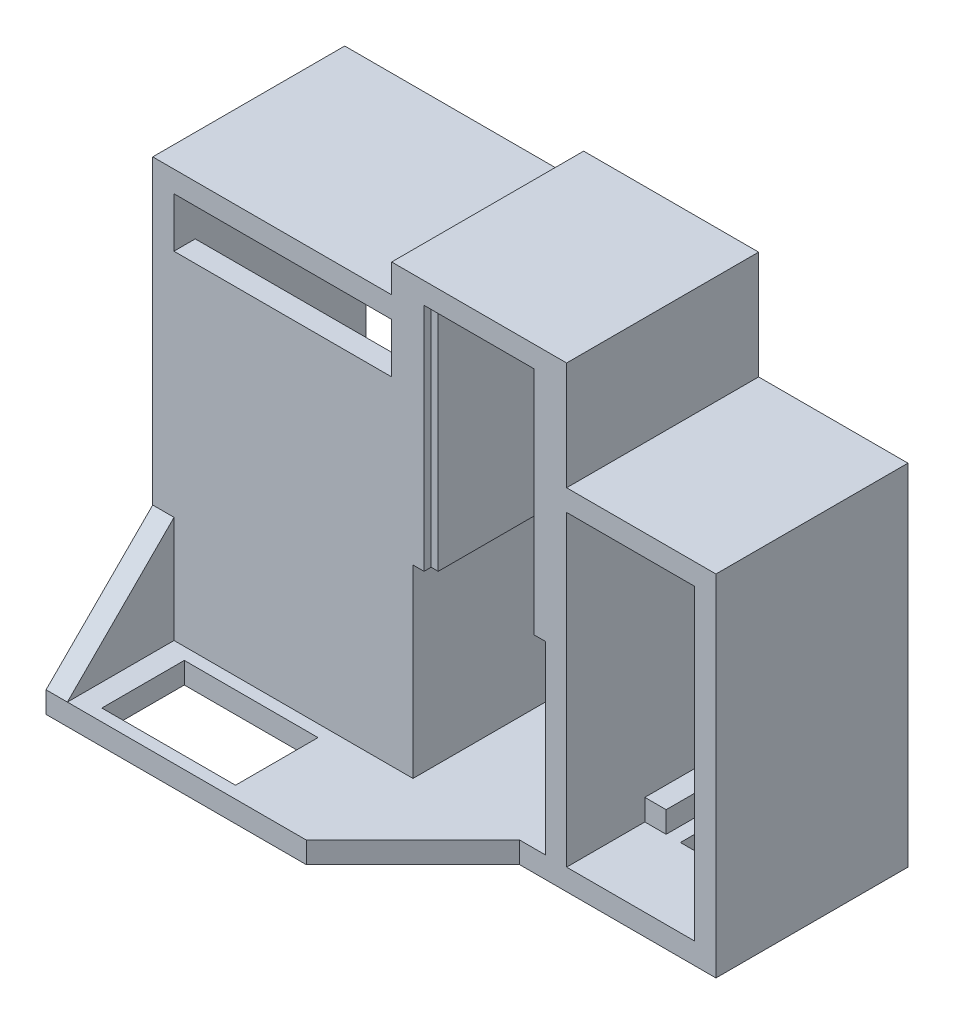
SolidWorks part; units mm, degrees
ref_plane "Front Plane" through (0, 0, 0) normal (0, 0, 1) x (1, 0, 0)
ref_plane "Top Plane" through (0, 0, 0) normal (0, 1, 0) x (1, 0, 0)
ref_plane "Right Plane" through (0, 0, 0) normal (1, 0, 0) x (0, 0, -1)
sketch "Sketch1" plane through (0, 0, 0) normal (0, 0, 1) x (1, 0, 0)
  line L0 (0, 0) -> (-18.6, 0)
  line L1 (-18.6, 0) -> (-18.6, 26)
  line L2 (-18.6, 26) -> (0, 26)
  line L3 (0, 26) -> (0, 0)
  line L4 (-18.6, 26) -> (-17.05, 26)
  line L5 (-17.05, 26) -> (-17.05, 58.4)
  line L6 (-17.05, 58.4) -> (-1.55, 58.4)
  line L7 (-1.55, 58.4) -> (-1.55, 26)
  line L8 (-18.6, 0) -> (-21.6, 0)
  line L9 (-21.6, 0) -> (-21.6, 58.4)
  line L10 (-21.6, 58.4) -> (-21.6, 61.4)
  line L11 (-21.6, 61.4) -> (-18.6, 61.4)
  line L12 (-18.6, 61.4) -> (-18.6, 26)
  line L13 (-18.6, 61.4) -> (0, 61.4)
  line L14 (0, 61.4) -> (0, 26)
  line L15 (0, 61.4) -> (3, 61.4)
  line L16 (3, 61.4) -> (3, 0)
  line L17 (3, 0) -> (0, 0)
  line L18 (3, 0) -> (3, -3)
  line L19 (3, -3) -> (-21.6, -3)
  line L20 (-21.6, -3) -> (-21.6, 0)
  line L21 (-21.6, 58.4) -> (3, 58.4)
  line L22 (-17.05, 58.4) -> (-16.05, 58.4)
  line L23 (-16.05, 58.4) -> (-16.05, 26)
  line L24 (-16.05, 26) -> (-17.05, 26)
  line L25 (-1.55, 58.4) -> (-2.55, 58.4)
  line L26 (-2.55, 58.4) -> (-2.55, 26)
  line L27 (-2.55, 26) -> (-1.55, 26)
extrude "Boss-Extrude1" add sketch "Sketch1" along normal blind 3 contours L23 L6 L5 L2 | L26 L21 L23 L2 | L6 L26 L2 L7 | L21 L7 L2 L14 | L21 L12 L2 L5 | L21 L9 L8 L1 L12 | L10 L21 L12 L11 | L12 L21 L6 L14 L13 | L14 L21 L16 L15 | L21 L14 L3 L17 L16 | L3 L2 L1 L0 | L20 L19 L18 L17 L0 L8 region at (-9.3, -1.5, 0) region at (-9.3, 13, 0) region at (1.5, 29.2, 0) region at (-20.1, 29.2, 0) region at (-0.775, 42.2, 0) region at (-17.825, 42.2, 0) region at (-2.05, 42.2, 0) region at (-9.3, 59.9, 0) region at (1.5, 59.9, 0) region at (-16.55, 42.2, 0) region at (-20.1, 59.9, 0) region at (-9.3, 42.2, 0)
extrude "Boss-Extrude2" add sketch "Sketch1<5>" along normal blind 26 contours L10 L21 L12 L11 | L12 L21 L6 L14 L13 | L6 L26 L2 L7 | L21 L7 L2 L14 | L23 L6 L5 L2 | L21 L12 L2 L5 | L21 L9 L8 L1 L12 | L14 L21 L16 L15 | L21 L14 L3 L17 L16 | L20 L19 L18 L17 L0 L8 region at (-9.3, -1.5, 0) region at (1.5, 29.2, 0) region at (-20.1, 29.2, 0) region at (-0.775, 42.2, 0) region at (-17.825, 42.2, 0) region at (-2.05, 42.2, 0) region at (-9.3, 59.9, 0) region at (1.5, 59.9, 0) region at (-16.55, 42.2, 0) region at (-20.1, 59.9, 0)
sketch "Sketch1<5>" plane through (0, 0, 0) normal (0, 0, 1) x (1, 0, 0) same geometry as "Sketch1"
extrude "Boss-Extrude4" add sketch "Sketch1<7>" along normal blind 35 contours L20 L19 L18 L17 L0 L8 region at (-9.3, -1.5, 0)
sketch "Sketch1<7>" plane through (0, 0, 0) normal (0, 0, 1) x (1, 0, 0) same geometry as "Sketch1"
extrude "Boss-Extrude5" add sketch "Sketch1<8>" along normal blind 27 contours L21 L12 L2 L5 | L21 L9 L8 L1 L12 | L10 L21 L12 L11 | L12 L21 L6 L14 L13 | L14 L21 L16 L15 | L21 L14 L3 L17 L16 | L21 L7 L2 L14 | L20 L19 L18 L17 L0 L8 region at (-9.3, -1.5, 0) region at (1.5, 29.2, 0) region at (-20.1, 29.2, 0) region at (-0.775, 42.2, 0) region at (-17.825, 42.2, 0) region at (-9.3, 59.9, 0) region at (1.5, 59.9, 0) region at (-20.1, 59.9, 0)
sketch "Sketch1<8>" plane through (0, 0, 0) normal (0, 0, 1) x (1, 0, 0) same geometry as "Sketch1"
sketch "Sketch2" plane through (0, 0, 0) normal (0, 0, -1) x (-1, 0, 0)
  line L0 (0, 0) -> (-3, 0)
  line L1 (-3, 0) -> (-3, -3)
  line L2 (-3, -3) -> (-21, -3)
  line L3 (-21, -3) -> (-21, 0)
  line L4 (-21, 0) -> (-3, 0)
  line L5 (-21, -3) -> (-24, -3)
  line L6 (-24, -3) -> (-24, 0)
  line L7 (-24, 0) -> (-21, 0)
  line L8 (-21, 0) -> (-21, 43.2)
  line L9 (-21, 43.2) -> (-3, 43.2)
  line L10 (-3, 61.4) -> (-3, 0) construction
  line L11 (-24, 0) -> (-24, 43.2)
  line L12 (-24, 43.2) -> (-24, 46.2)
  line L13 (-24, 46.2) -> (-3, 46.2)
  line L14 (-3, 46.2) -> (-3, 0)
  line L15 (-21, 43.2) -> (-21, 40.2)
  line L16 (-21, 40.2) -> (-16, 40.2)
  line L17 (-16, 40.2) -> (-16, 43.2)
  line L18 (-3, 43.2) -> (-3, 40.2)
  line L19 (-3, 40.2) -> (-8, 40.2)
  line L20 (-8, 40.2) -> (-8, 43.2)
  line L21 (-21, 0) -> (-18, 0)
  line L22 (-18, 0) -> (-18, 3)
  line L23 (-18, 3) -> (-21, 3)
  line L24 (-3, 0) -> (-3, 3)
  line L25 (-3, 3) -> (-6, 3)
  line L26 (-6, 3) -> (-6, 0)
  line L27 (-21, -3) -> (-16, -3)
  line L28 (-16, -3) -> (-16, 0)
  line L29 (-3, -3) -> (-8, -3)
  line L30 (-8, -3) -> (-8, 0)
  line M8 (-3, 61.4) -> (-3, -3)
extrude "Boss-Extrude6" add sketch "Sketch2" against normal blind 3 contours L26 L25 L14 L19 L20 L9 L17 L16 L8 L23 L22 L4 region at (12, 21.2694, 0)
extrude "Boss-Extrude7" add sketch "Sketch2<3>" against normal blind 2 contours L25 L26 L4 M8 | L30 L2 L4 M8 | L22 L23 L8 L4 | L2 L28 L4 L3 | L7 L6 L5 L3 | L13 L12 L11 L7 L8 L9 M8 | L16 L17 L9 L8 | L20 L19 L9 M8 region at (5.5, -1.5, 0) region at (4.5, 1.5, 0) region at (5.5, 41.7, 0) region at (18.5, -1.5, 0) region at (5.5, 43.7075, 0) region at (22.5, -1.5, 0) region at (19.5, 1.5, 0) region at (18.5, 41.7, 0)
sketch "Sketch2<3>" plane through (0, 0, 0) normal (0, 0, -1) x (-1, 0, 0) same geometry as "Sketch2"
extrude "Boss-Extrude8" add sketch "Sketch2<4>" against normal blind 11 contours L2 L30 L4 L28 region at (12, -1.5, 0)
sketch "Sketch2<4>" plane through (0, 0, 0) normal (0, 0, -1) x (-1, 0, 0) same geometry as "Sketch2"
extrude "Boss-Extrude9" add sketch "Sketch2<5>" against normal blind 27 contours L30 L2 L4 M8 | L2 L28 L4 L3 | L7 L6 L5 L3 | L13 L12 L11 L7 L8 L9 M8 region at (5.5, -1.5, 0) region at (18.5, -1.5, 0) region at (5.5, 43.7075, 0) region at (22.5, -1.5, 0)
sketch "Sketch2<5>" plane through (0, 0, 0) normal (0, 0, -1) x (-1, 0, 0) same geometry as "Sketch2"
sketch "Sketch5" plane through (0, 0, 0) normal (0, 0, -1) x (-1, 0, 0)
  line L0 (21.6, -3) -> (52.2188, -3)
  line L1 (52.2188, -3) -> (52.2188, 57.4)
  line L2 (52.2188, 57.4) -> (21.6, 57.4)
  line L3 (21.6, 0) -> (21.6, 61.4) construction
  line L4 (21.6, 57.4) -> (21.6, 54.4)
  line L5 (21.6, 54.4) -> (21.6, 0)
  line L6 (21.6, 0) -> (21.6, -3)
  line L7 (21.6, 0) -> (52.2188, 0)
  line L8 (52.2188, -3) -> (55.2, -3)
  line L9 (55.2, -3) -> (55.2, 57.4)
  line L10 (55.2, 57.4) -> (52.2188, 57.4)
  line L11 (52.2188, 57.4) -> (52.2188, 54.4)
  line L12 (52.2188, 54.4) -> (21.6, 54.4)
  line M11 (21.6, -3) -> (21.6, 61.4)
extrude "Boss-Extrude11" add sketch "Sketch5" against normal blind 3 contours L12 L1 L2 M11 | L9 L10 L1 L8 | L7 L0 L1 M11 | L1 L12 L7 M11 region at (-36.9094, -1.5, 0) region at (-53.7094, 27.2, 0) region at (-36.9094, 27.2, 0) region at (-36.9094, 55.9, 0)
extrude "Cut-Extrude3" cut sketch "Sketch5<5>" against normal blind 3 contours L1 L12 L7 M11 region at (-36.9094, 27.2, 0)
sketch "Sketch5<5>" plane through (0, 0, 0) normal (0, 0, -1) x (-1, 0, 0) same geometry as "Sketch5"
extrude "Boss-Extrude12" add sketch "Sketch5<6>" against normal blind 27 contours L12 L1 L2 M11 | L9 L10 L1 L8 | L7 L0 L1 M11 region at (-36.9094, -1.5, 0) region at (-53.7094, 27.2, 0) region at (-36.9094, 55.9, 0)
sketch "Sketch5<6>" plane through (0, 0, 0) normal (0, 0, -1) x (-1, 0, 0) same geometry as "Sketch5"
sketch "Sketch6" plane through (0, 0, 27) normal (0, 0, 1) x (1, 0, 0)
  line L0 (-21.6, 54.4) -> (-21.6, 47.4)
  line L1 (-21.6, 0) -> (-21.6, 54.4) construction
  line L2 (-21.6, 47.4) -> (-52.2188, 47.4)
  line L3 (-52.2188, 0) -> (-52.2188, 54.4) construction
  line L4 (-52.2188, 47.4) -> (-52.2188, 0)
  line L5 (-52.2188, 0) -> (-21.6, 0)
  line L6 (-21.6, 0) -> (-21.6, 47.4)
  line M21 (-21.6, 0) -> (-52.2188, 0)
  line M22 (-52.2188, 0) -> (-52.2188, 54.4)
  line M24 (-21.6, 54.4) -> (-21.6, 0)
extrude "Boss-Extrude13" add sketch "Sketch6" against normal blind 3 contours L2 M24 M22 M21 region at (-36.9094, 23.7, 27)
sketch "Sketch7" plane through (0, -3, 0) normal (0, -1, 0) x (1, 0, 0)
  line L0 (-21.6, 27) -> (-21.6, 35)
  line L1 (-21.6, 35) -> (3, 35)
  line L2 (3, 35) -> (3, 27)
  line L3 (3, 27) -> (-21.6, 27)
extrude "Cut-Extrude4" cut sketch "Sketch7" against normal blind 3
sketch "Sketch8" plane through (8, 0, 0) normal (1, 0, 0) x (0, 0, -1)
  line L0 (-11, -3) -> (-16, -3)
  line L1 (-27, -3) -> (0, -3) construction
  line L2 (-16, -3) -> (-16, 0)
  line L3 (-27, 0) -> (-11, 0) construction
  line L4 (-16, 0) -> (-27, 0)
  line L5 (-27, 0) -> (-27, -3)
  line L6 (-27, -3) -> (-16, -3)
  line M1 (-27, -3) -> (-11, -3)
  line M3 (-11, 0) -> (-27, 0)
  line M4 (-27, 0) -> (-27, -3)
extrude "Boss-Extrude14" add sketch "Sketch8" along normal blind 8 contours L2 M1 M3 M4 region at (8, -1.5, 21.5)
extrude "Boss-Extrude15" add sketch "Sketch2<6>" against normal blind 16 contours L20 L19 L9 M8 | L16 L17 L9 L8 | L22 L23 L8 L4 | L25 L26 L4 M8 region at (4.5, 1.5, 0) region at (5.5, 41.7, 0) region at (19.5, 1.5, 0) region at (18.5, 41.7, 0)
sketch "Sketch2<6>" plane through (0, 0, 0) normal (0, 0, -1) x (-1, 0, 0) same geometry as "Sketch2"
sketch "Sketch9" plane through (0, 0, 27) normal (0, 0, 1) x (1, 0, 0)
  line L0 (-18.6, 0) -> (-18.6, -3)
  line L1 (-55.2, -3) -> (24, -3) construction
  line L2 (-18.6, -3) -> (-55.2, -3)
  line L3 (-55.2, -3) -> (-55.2, 0)
  line L4 (-55.2, -3) -> (-55.2, 57.4) construction
  line L5 (-55.2, 0) -> (-18.6, 0)
extrude "Boss-Extrude16" add sketch "Sketch9" along normal blind 15
sketch "Sketch10" plane through (0, -3, 0) normal (0, -1, 0) x (-1, 0, 0)
  line L0 (18.6, -27) -> (55.2, -27)
  line L1 (55.2, -42) -> (55.2, 0) construction
  line L2 (18.6, -27) -> (30.2563, -27)
  line L3 (30.2563, -27) -> (30.2563, -28.7)
  line L4 (30.2563, -28.7) -> (30.2563, -40.3018)
  line L5 (30.2563, -40.3018) -> (49.0563, -40.3018)
  line L6 (49.0563, -40.3018) -> (49.0563, -28.7)
  line L7 (49.0563, -28.7) -> (30.2563, -28.7)
  dimension "D1" = 1.7
extrude "Cut-Extrude5" cut sketch "Sketch10" against normal blind 15 contours L6 L7 L4 L5 region at (-39.6563, -3, 34.5009)
sketch "Sketch11" plane through (0, -3, 0) normal (0, -1, 0) x (-1, 0, 0)
  line L0 (18.6, -42) -> (18.6, -27)
  line L1 (18.6, -42) -> (3.6, -27)
  line L2 (18.6, -27) -> (-24, -27) construction
  line L3 (3.6, -27) -> (18.6, -27)
extrude "Boss-Extrude17" add sketch "Sketch11" against normal blind 3
sketch "Sketch12" plane through (-55.2, 0, 0) normal (-1, 0, 0) x (0, 0, 1)
  line L0 (27, 0) -> (42, 0)
  line L1 (42, 0) -> (27, 15)
  line L2 (27, 0) -> (27, 57.4) construction
  line L3 (27, 15) -> (27, 0)
extrude "Boss-Extrude18" add sketch "Sketch12" against normal blind 3
